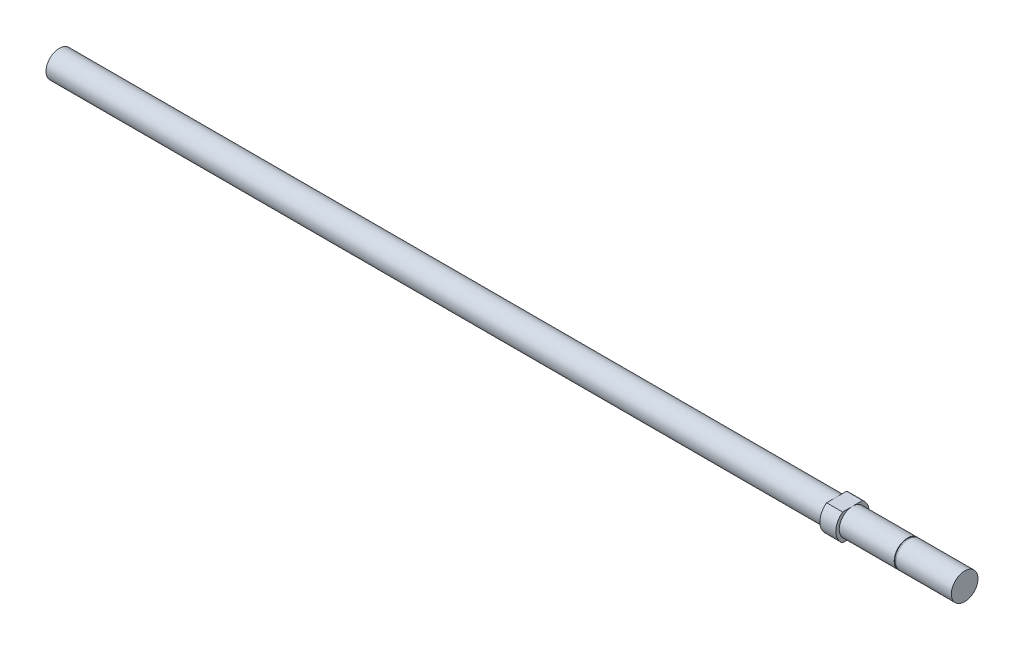
SolidWorks part; units mm, degrees
ref_plane "XY" through (0, 0, 0) normal (0, 0, 1) x (1, 0, 0)
ref_plane "XZ" through (0, 0, 0) normal (0, 1, 0) x (1, 0, 0)
ref_plane "YZ" through (0, 0, 0) normal (1, 0, 0) x (0, 0, -1)
ref_axis "X" through (-226.1616, 0, 0) along (1, 0, 0)
ref_axis "Y" through (0, -3.4925, 0) along (0, 1, 0)
ref_axis "Z" through (0, 0, 4.3656) along (0, 0, -1)
sketch "Sketch1" plane through (0, 0, 0) normal (0, 0, 1) x (1, 0, 0)
  line L0 (0, 0) -> (-215.392, 0)
  line L1 (-215.392, 0) -> (-215.392, 3.175)
  line L2 (-215.392, 3.175) -> (-30.48, 3.175)
  line L3 (-30.48, 3.175) -> (-30.48, 3.9687)
  line L4 (-30.48, 3.9687) -> (-26.67, 3.9687)
  line L5 (-26.67, 3.9687) -> (-26.67, 3.175)
  line L6 (-26.67, 3.175) -> (-13.589, 3.175)
  line L7 (0, 3.175) -> (0, 0)
  line L8 (-13.589, 3.175) -> (-13.589, 3.0226)
  line L9 (-13.589, 3.0226) -> (-13.208, 3.0226)
  line L10 (-13.208, 3.0226) -> (-13.208, 3.175)
  line L11 (-13.208, 3.175) -> (0, 3.175)
  dimension "D1" = 184.912
  dimension "D2" = 3.81
  dimension "D3" = 13.081
  dimension "D4" = 3.175
  dimension "D5" = 3.9688
  dimension "D6" = 3.0226
  dimension "D7" = 0.381
  dimension "D8" = 30.48
revolve "Revolve1" add sketch "Sketch1" angle 360 about L0
sketch "Sketch2" plane through (0, 0, 0) normal (1, 0, 0) x (0, 0, -1)
  line L1 (-3.9688, -3.175) -> (3.9688, -3.175)
  line L2 (-3.9688, -3.175) -> (-3.9688, 3.175)
  line L3 (-3.9688, 3.175) -> (3.9688, 3.175)
  line L4 (3.9688, -3.175) -> (3.9688, 3.175)
  circle A0 centre (0, 0) radius 3.175 construction
  circle A1 centre (0, 0) radius 3.9687 construction
extrude "Cut-Extrude1" cut sketch "Sketch2" against normal through all flip side to cut
sketch "Sketch3" [suppressed] plane through (-30.48, 0, 0) normal (-1, 0, 0) x (0, 0, 1)
  arc A0 (0, -3.175) -> (0, 3.175) centre (0, 0) ccw
  arc A1 (0, 3.175) -> (0, -3.175) centre (0, 0) ccw
  arc A2 (0, 3.175) -> (0, -3.175) centre (0, 0) ccw
  arc A3 (0, -3.175) -> (0, 3.175) centre (0, 0) ccw
extrude "Cut-Extrude2" [suppressed] cut sketch "Sketch3" against normal through all from offset 17.78 offset against normal yes
